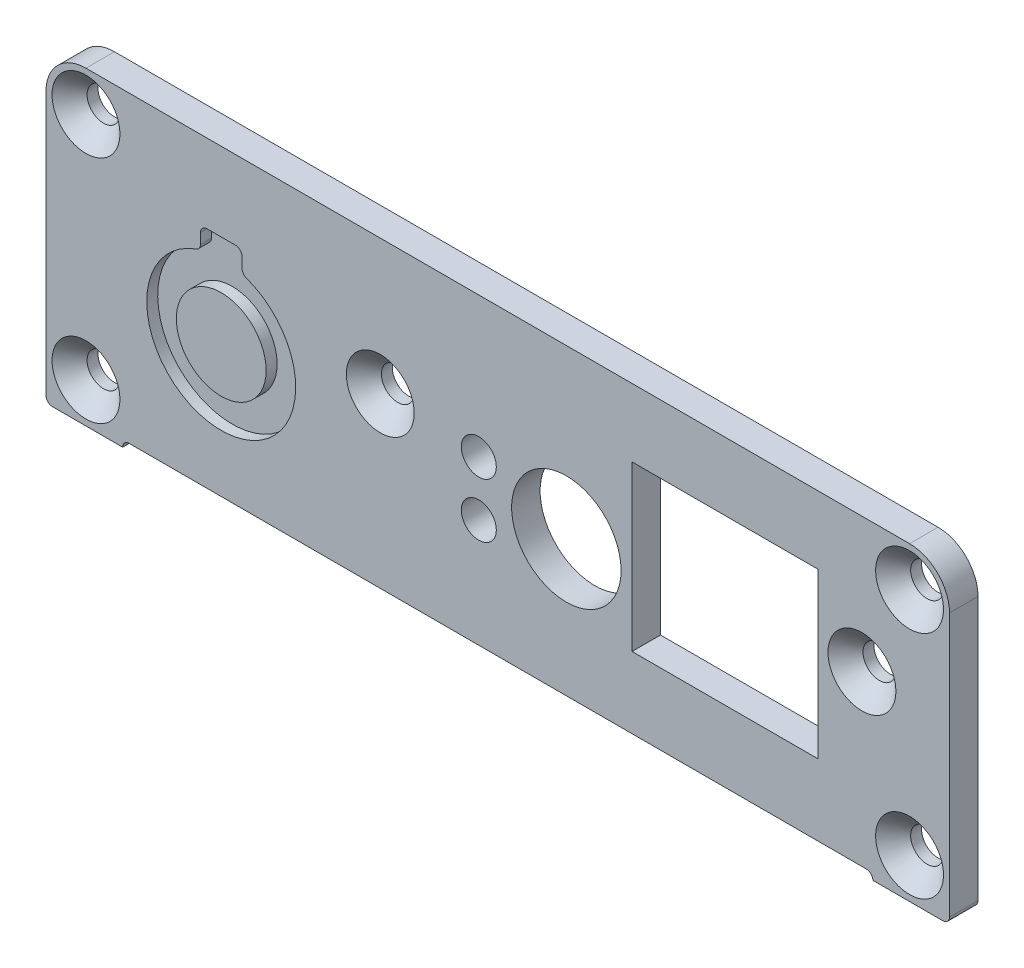
SolidWorks part; units mm, degrees
ref_plane "Front Plane" through (0, 0, 0) normal (0, 0, 1) x (1, 0, 0)
ref_plane "Top Plane" through (0, 0, 0) normal (0, 1, 0) x (1, 0, 0)
ref_plane "Right Plane" through (0, 0, 0) normal (1, 0, 0) x (0, 0, -1)
sketch "Sketch1" plane through (0, 0, 0) normal (0, 0, 1) x (1, 0, 0)
  line L0 (7, 0) -> (7, 0.6)
  line L1 (0, 0) -> (7, 0)
  line L2 (0, 0) -> (0, 28.3)
  line L3 (0, 28.3) -> (82.5, 28.3)
  line L4 (82.5, 0) -> (82.5, 28.3)
  line L5 (7, 0.6) -> (75.5, 0.6)
  line L6 (75.5, 0.6) -> (75.5, 0)
  line L7 (75.5, 0) -> (82.5, 0)
  circle A0 centre (3.65, 24.65) radius 1.5
  circle A1 centre (3.65, 3.65) radius 1.5
  circle A2 centre (78.85, 24.65) radius 1.5
  circle A3 centre (78.85, 3.65) radius 1.5
  dimension "D6" = 3
  dimension "D7" = 3
  dimension "D8" = 3
  dimension "D9" = 3
  dimension "D1" = 82.5
  dimension "D2" = 28.3
  dimension "D3" = 7
  dimension "D4" = 7
  dimension "D5" = 0.6
  dimension "D10" = 21
  dimension "D11" = 21
  dimension "D12" = 3.65
  dimension "D13" = 3.65
  dimension "D14" = 3.65
  dimension "D15" = 3.65
extrude "Boss-Extrude1" add sketch "Sketch1" along normal blind 2.6
fillet "Fillet1" radius 3.65 2 edges at (82.5, 28.3, 1.3) (0, 28.3, 1.3)
fillet "Fillet2" radius 0.6 4 edges at (75.5, 0.6, 1.3) (82.5, 0, 1.3) (7, 0.6, 1.3) (0, 0, 1.3)
chamfer "Chamfer1" distance 1.6 angle 45 4 edges at (80.35, 3.65, 2.6) (80.35, 24.65, 2.6) (5.15, 3.65, 2.6) (5.15, 24.65, 2.6)
sketch "Sketch2" plane through (0, 0, 2.6) normal (0, 0, 1) x (1, 0, 0)
  line L0 (75.5, 0) -> (81.9, 0) construction
  line L1 (53.5107, 22.0969) -> (70.502, 22.0969)
  line L2 (53.5107, 22.0969) -> (53.5107, 7.1045)
  line L3 (53.5107, 7.1045) -> (70.502, 7.1045)
  line L4 (70.502, 22.0969) -> (70.502, 7.1045)
  line L5 (82.5, 0.6) -> (82.5, 24.65) construction
  line L6 (30.5225, 6.305) -> (51.2157, 6.305) construction
  line L7 (30.5225, 6.305) -> (30.5225, 24.6942) construction
  circle A0 centre (74.5, 16) radius 1.4992
  circle A1 centre (30.5225, 16) radius 1.4992
  circle A2 centre (47.5138, 13.0015) radius 4.9974
  circle A3 centre (39.5179, 15.5003) radius 1.5992
  circle A4 centre (39.5179, 10.5028) radius 1.5992
  dimension "D11" = 2.9985
  dimension "D12" = 2.9985
  dimension "D13" = 9.9949
  dimension "D8" = 3.1984
  dimension "D19" = 3.1984
  dimension "D2" = 14.9923
  dimension "D3" = 0.7996
  dimension "D4" = 6.6966
  dimension "D5" = 16.9913
  dimension "D6" = 4.1979
  dimension "D7" = 9.1953
  dimension "D9" = 9.695
  dimension "D10" = 9.695
  dimension "D14" = 8.9954
  dimension "D15" = 43.9775
  dimension "D16" = 8.9954
  dimension "D17" = 16.9913
  dimension "D18" = 39.9796
  dimension "D20" = 16
  dimension "D21" = 8
extrude "Cut-Extrude1" cut sketch "Sketch2" against normal blind 2.6
chamfer "Chamfer2" distance 1.6 angle 45 2 edges at (75.9992, 16, 2.6) (32.0217, 16, 2.6)
sketch "Sketch3" plane through (0, 0, 2.6) normal (0, 0, 1) x (1, 0, 0)
  line L0 (0, 12.625) -> (82.5, 12.625) construction
  line L1 (0, 24.65) -> (0, 0.6) construction
  line L2 (82.5, 0.6) -> (82.5, 24.65) construction
  circle A0 centre (16, 12.625) radius 6.8
  dimension "D1" = 13.6
  dimension "D2" = 16
extrude "Cut-Extrude2" cut sketch "Sketch3" against normal blind 1
sketch "Sketch4" plane through (0, 0, 1.6) normal (0, 0, 1) x (1, 0, 0)
  circle A0 centre (16, 12.625) radius 4.1
  dimension "D1" = 8.2
extrude "Cut-Extrude3" cut sketch "Sketch4" against normal blind 3
sketch "Sketch5" plane through (0, 0, 2.6) normal (0, 0, 1) x (1, 0, 0)
  line L0 (16, 12.625) -> (16, 24.1527) construction
  line L2 (14.1, 21.125) -> (17.9, 21.125)
  line L3 (14.1, 21.125) -> (14.1, 17.7339)
  line L4 (14.1, 17.7339) -> (17.9, 17.7339)
  line L5 (17.9, 21.125) -> (17.9, 17.7339)
  dimension "D3" = 8.5
  dimension "D1" = 3.8
  dimension "D2" = 1.9
extrude "Cut-Extrude4" cut sketch "Sketch5" against normal blind 1
fillet "Fillet3" radius 0.6 4 edges at (17.9, 19.1542, 2.1) (14.1, 19.1542, 2.1) (17.9, 21.125, 2.1) (14.1, 21.125, 2.1)
sketch "Sketch6" plane through (0, 0, 1.6) normal (0, 0, 1) x (1, 0, 0)
  circle A0 centre (16, 12.625) radius 4.1
extrude "Boss-Extrude3" add sketch "Sketch6" along normal blind 1 separate body
